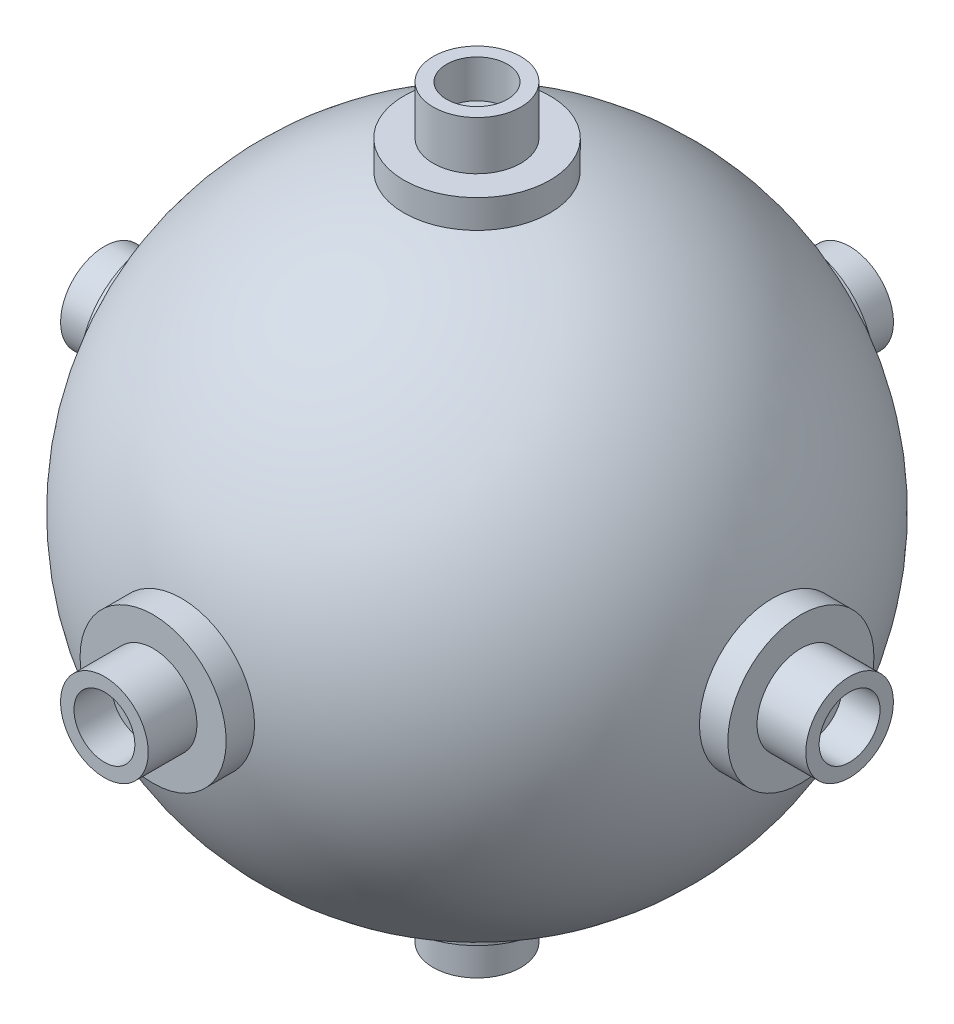
SolidWorks part; units mm, degrees
ref_plane "Front Plane" through (0, 0, 0) normal (0, 0, 1) x (1, 0, 0)
ref_plane "Top Plane" through (0, 0, 0) normal (0, 1, 0) x (1, 0, 0)
ref_plane "Right Plane" through (0, 0, 0) normal (1, 0, 0) x (0, 0, -1)
sketch "Sketch1" plane through (0, 0, 0) normal (0, 0, 1) x (1, 0, 0)
  line L0 (0, 15.875) -> (0, -15.875)
  arc A0 (0, 15.875) -> (0, -15.875) centre (0, 0) ccw
revolve "Revolve1" add sketch "Sketch1" angle 360 about L0 region at (-6.7376, 0, 0)
sketch "Sketch2" plane through (0, 0, 0) normal (0, 0, 1) x (1, 0, 0)
  circle A0 centre (0, 0) radius 15.875 construction
  point P0 (0, 15.875)
  point P1 (0, -15.875)
  point P4 (15.875, 0)
  point P5 (-15.875, 0)
sketch "Sketch5" plane through (0, 0, 0) normal (1, 0, 0) x (0, 0, -1)
  circle A0 centre (0, 0) radius 15.875 construction
  point P0 (-15.875, 0)
  point P1 (15.875, 0)
ref_plane "Plane2" through (0, 0, 15.875) normal (0, 0, 1) x (1, 0, 0)
sketch "Sketch6" plane through (0, 0, 15.875) normal (0, 0, 1) x (1, 0, 0)
  circle A0 centre (0, 0) radius 3.81
extrude "Boss-Extrude1" add sketch "Sketch6" along normal mid plane 2.032 contours A0
sketch "Sketch7" plane through (0, 0, 0) normal (0, 0, 1) x (1, 0, 0)
  line L0 (0, 15.875) -> (0, -15.875) construction
sketch "Sketch9" plane through (0, 0, 16.891) normal (0, 0, 1) x (1, 0, 0)
  circle A0 centre (0, 0) radius 2.286
extrude "Boss-Extrude3" add sketch "Sketch9" along normal blind 2.54
pattern_circular "CirPattern1" count 4 over 360 about axis through (0, 15.875, 0) along (0, -1, 0) of "Boss-Extrude1", "Boss-Extrude3"
ref_plane "Plane3" through (0, 15.875, 0) normal (0, 1, 0) x (1, 0, 0)
sketch "Sketch10" plane through (0, 15.875, 0) normal (0, 1, 0) x (1, 0, 0)
  circle A0 centre (0, 0) radius 3.81
extrude "Boss-Extrude4" add sketch "Sketch10" along normal mid plane 2.032
sketch "Sketch11" plane through (0, 16.891, 0) normal (0, 1, 0) x (1, 0, 0)
  circle A0 centre (0, 0) radius 2.286
extrude "Boss-Extrude5" add sketch "Sketch11" along normal blind 2.54
mirror "Mirror1" about plane through (0, 0, 0) normal (0, 1, 0) of "Boss-Extrude4", "Boss-Extrude5"
hole_wizard "CBORE for #00 Binding Head Machine Screw1" positions "Sketch12" profile "Sketch13" counterbore size "#00" standard "ANSI Inch"
sketch "Sketch12" plane through (0, 19.431, 0) normal (0, 1, 0) x (1, 0, 0)
  point P0 (0, 0)
sketch "Sketch13" plane through (0, 19.431, 0) normal (1, 0, 0) x (0, 0, 1)
  line L0 (0, 0) -> (0, 4.2297)
  line L1 (0, 4.2297) -> (0.6985, 3.81)
  line L2 (0.6985, 3.81) -> (0.6985, 1.9812)
  line L3 (0.6985, 1.9812) -> (1.5875, 1.9812)
  line L4 (1.5875, 1.9812) -> (1.5875, 0)
  line L5 (1.5875, 0) -> (0, 0)
  line L10 (0, 4.2297) -> (-0.6985, 3.81) construction
  line L11 (0, -6.35) -> (0, 107.95) construction
  dimension "Hole Dia." = 1.397
  dimension "Hole Depth" = 3.81
  dimension "C'Bore Dia." = 3.175
  dimension "C'Bore Depth" = 1.9812
  dimension "Drill Angle" = 118
sketch "Sketch15" plane through (0, 0, 0) normal (0, 1, 0) x (1, 0, 0)
  line L0 (-15.875, 0) -> (15.875, 0) construction
pattern_circular "CirPattern2" count 4 every 90 about axis through (-15.875, 0, 0) along (1, 0, 0) of "CBORE for #00 Binding Head Machine Screw1" reverse direction yes
hole_wizard "CBORE for #00 Binding Head Machine Screw3" positions "Sketch18" profile "Sketch19" counterbore size "#00" standard "ANSI Inch"
sketch "Sketch18" plane through (19.431, 0, 0) normal (1, 0, 0) x (0, 0, -1)
  point P0 (0, 0)
sketch "Sketch19" plane through (19.431, 0, 0) normal (0, 1, 0) x (0, 0, -1)
  line L0 (0, 0) -> (0, 4.2297)
  line L1 (0, 4.2297) -> (0.6985, 3.81)
  line L2 (0.6985, 3.81) -> (0.6985, 1.9812)
  line L3 (0.6985, 1.9812) -> (1.5875, 1.9812)
  line L4 (1.5875, 1.9812) -> (1.5875, 0)
  line L5 (1.5875, 0) -> (0, 0)
  line L10 (0, 4.2297) -> (-0.6985, 3.81) construction
  line L11 (0, -6.35) -> (0, 107.95) construction
  dimension "Hole Dia." = 1.397
  dimension "Hole Depth" = 3.81
  dimension "C'Bore Dia." = 3.175
  dimension "C'Bore Depth" = 1.9812
  dimension "Drill Angle" = 118
mirror "Mirror2" about plane through (0, 0, 0) normal (1, 0, 0) of "CBORE for #00 Binding Head Machine Screw3"
